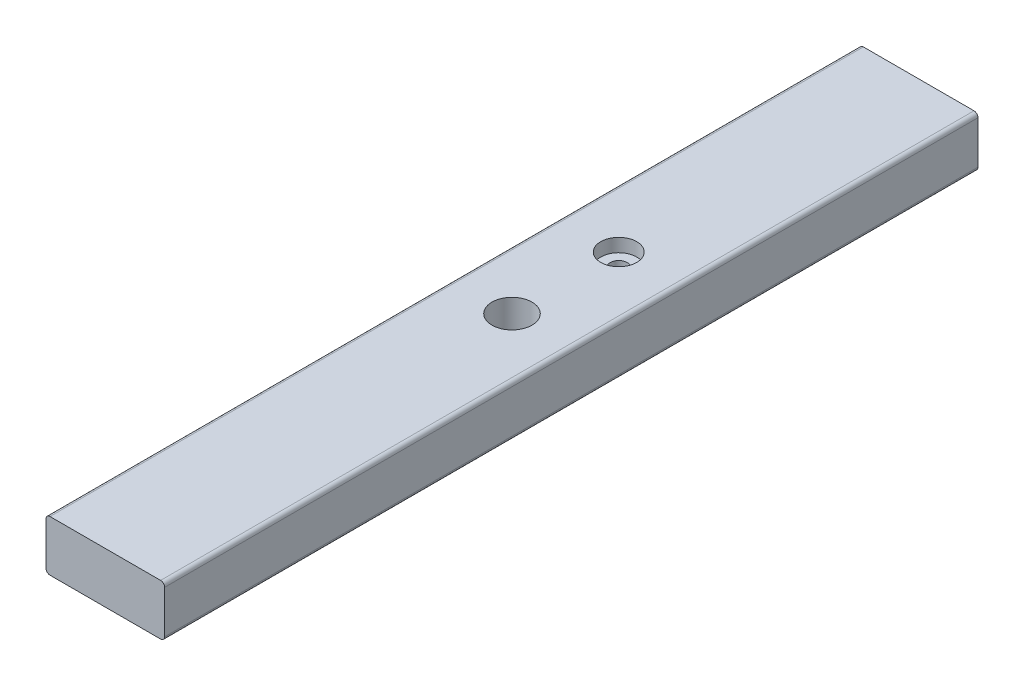
SolidWorks part; units mm, degrees
ref_plane "Front Plane" through (0, 0, 0) normal (0, 0, 1) x (1, 0, 0)
ref_plane "Top Plane" through (0, 0, 0) normal (0, 1, 0) x (1, 0, 0)
ref_plane "Right Plane" through (0, 0, 0) normal (1, 0, 0) x (0, 0, -1)
sketch "Sketch1" plane through (0, 0, 0) normal (0, 0, 1) x (1, 0, 0)
  line L1 (41.45, -19.05) -> (-41.45, -19.05)
  line L2 (44.45, -16.05) -> (44.45, 16.05)
  line L3 (41.45, 19.05) -> (-41.45, 19.05)
  line L4 (-44.45, -16.05) -> (-44.45, 16.05)
  line L5 (44.45, -19.05) -> (-44.45, 19.05) construction
  line L6 (44.45, 19.05) -> (-44.45, -19.05) construction
  arc A0 (-41.45, -19.05) -> (-44.45, -16.05) centre (-41.45, -16.05) cw
  arc A1 (-41.45, 19.05) -> (-44.45, 16.05) centre (-41.45, 16.05) ccw
  arc A2 (44.45, 16.05) -> (41.45, 19.05) centre (41.45, 16.05) ccw
  arc A3 (41.45, -19.05) -> (44.45, -16.05) centre (41.45, -16.05) ccw
  point P0 (0, 0)
  dimension "D3" = 3
  dimension "D1" = 88.9
  dimension "D2" = 38.1
extrude "Boss-Extrude1" add sketch "Sketch1" along normal blind 609.6
sketch "Sketch2" plane through (0, 19.05, 0) normal (0, 1, 0) x (1, 0, 0)
  line L0 (-41.45, -609.6) -> (-41.45, 0) construction
  circle A0 centre (0, -304.8) radius 15
  circle A1 centre (0, -224.8) radius 6.35
  point P4 (0, 0)
  point P6 (0, -225.3815)
  point P7 (0, -336.1571)
  point P10 (-41.45, -304.8)
  dimension "D1" = 30
  dimension "D2" = 12.7
  dimension "D3" = 80
extrude "Cut-Extrude1" cut sketch "Sketch2" against normal through all
sketch "Sketch3" plane through (0, 19.05, 0) normal (0, 1, 0) x (1, 0, 0)
  circle A0 centre (0, -224.8) radius 13.5001
  dimension "D1" = 27.0002
extrude "Cut-Extrude2" cut sketch "Sketch3" against normal blind 10
mirror "Mirror1" about plane through (0, 0, 0) normal (0, 1, 0) of "Cut-Extrude2"
equation "\"ChainSeperation\"= 80"
